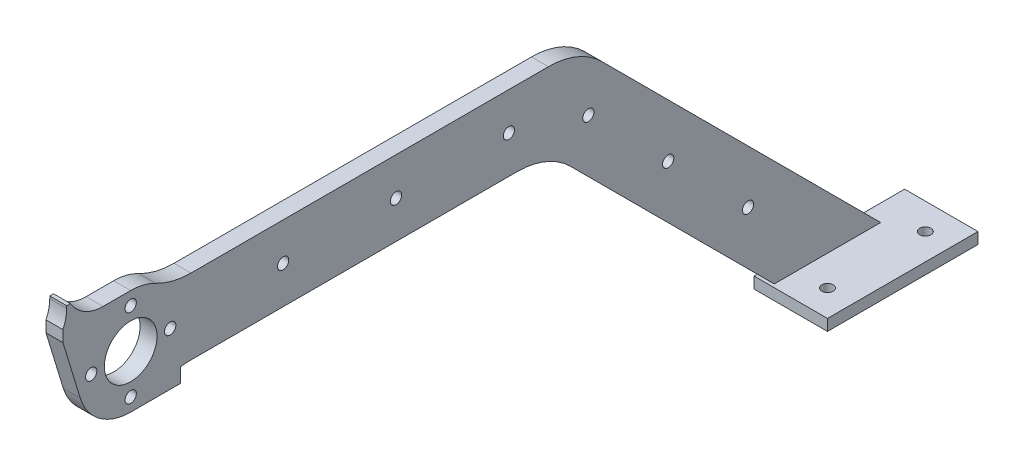
SolidWorks part; units mm, degrees
ref_plane "前视基准面" through (0, 0, 0) normal (0, 0, 1) x (1, 0, 0)
ref_plane "上视基准面" through (0, 0, 0) normal (0, 1, 0) x (1, 0, 0)
ref_plane "右视基准面" through (0, 0, 0) normal (1, 0, 0) x (0, 0, -1)
sketch "草图1" plane through (0, 0, 0) normal (1, 0, 0) x (0, 0, -1)
  line L2 (116.8579, -15.8579) -> (171, -70)
  line L3 (171, -70) -> (199.2843, -70)
  line L4 (199.2843, -70) -> (125.1421, 4.1421)
  line L5 (111, 10) -> (16, 10)
  line L7 (16, -10) -> (102.7369, -10)
  line L8 (186.193, -71.0509) -> (123.8062, -8.664) construction
  line L9 (0, 14) -> (-18, 14)
  line L10 (-18, 14) -> (-18, 11)
  line L11 (-18, 11) -> (-13.3889, -4.091)
  line L12 (13.2242, -14) -> (13.2242, -10)
  line L13 (0, -14) -> (13.2242, -14)
  arc A0 (6.5882, 12.3529) -> (6.5882, -12.3529) centre (0, 0) ccw
  circle A1 centre (0, 0) radius 10.5 construction
  circle A2 centre (0, 0) radius 7
  circle A3 centre (0, 10.5) radius 1.5
  circle A4 centre (10.5, 0) radius 1.5
  circle A5 centre (0, -10.5) radius 1.5
  circle A6 centre (-10.5, 0) radius 1.5
  arc A7 (125.1421, 4.1421) -> (111, 10) centre (111, -10) ccw
  arc A8 (102.7369, -10) -> (116.8579, -15.8579) centre (102.7157, -30) cw
  circle A9 centre (40.5, 0) radius 1.5
  circle A10 centre (70.5, 0) radius 1.5
  circle A11 centre (100.5, 0) radius 1.5
  circle A12 centre (121.61, -6.4679) radius 1.5
  circle A13 centre (142.8232, -27.6811) radius 1.5
  circle A14 centre (164.0364, -48.8943) radius 1.5
  arc A15 (16, 10) -> (6.5882, 12.3529) centre (16, 30) cw
  arc A16 (16, -10) -> (6.5882, -12.3529) centre (16, -30) ccw
  point P36 (185.1421, -70)
  point P43 (9.798, 7.7889)
  point P50 (9.798, -10)
  dimension "D1" = 28
  dimension "D2" = 21
  dimension "D3" = 14
  dimension "D4" = 3
  dimension "D9" = 20
  dimension "D13" = 3
  dimension "D16" = 30
  dimension "D17" = 3
  dimension "D19" = 30
  dimension "D24" = 20
  dimension "D25" = 20
  dimension "D6" = 135
  dimension "D7" = 20
  dimension "D8" = 171
  dimension "D10" = 70
  dimension "D11" = 20
  dimension "D14" = 40.5
  dimension "D18" = 21.11
  dimension "D20" = 30
  dimension "D21" = 18
  dimension "D22" = 3
  dimension "D26" = 13.2242
  dimension "D28" = 20
  dimension "D15" = 3
  dimension "D5" = 4
extrude "凸台-拉伸1" add sketch "草图1" along normal mid plane 4.5 contours A16 L7 A8 L2 L3 L4 A7 L5 A15 A0 A14 A13 A12 A11 A10 A9 A6 A5 A4 A3 A2 | A0 L9 L10 L11 | L12 A16 A0 region at (0, -9.4091, -111.2575) region at (0, -12.6228, -9.4909) region at (0, 9.7023, 13.097)
sketch "草图5" plane through (0, -70, 0) normal (0, -1, 0) x (1, 0, 0)
  line L0 (-2.25, -116.8579) -> (-2.25, -171) construction
  line L1 (-2.25, -170.1443) -> (17.25, -170.1443)
  line L2 (-2.25, -170.1443) -> (-2.25, -210.1443)
  line L3 (-2.25, -210.1443) -> (17.25, -210.1443)
  line L4 (17.25, -170.1443) -> (17.25, -210.1443)
  line L5 (2.25, -199.2843) -> (-2.25, -199.2843) construction
  dimension "D1" = 19.5
  dimension "D2" = 40
  dimension "D3" = 10.86
extrude "凸台-拉伸3" add sketch "草图5" along normal blind 3
sketch "草图6" plane through (0, -70, 0) normal (0, 1, 0) x (1, 0, 0)
  line L0 (17.25, 190.1443) -> (-2.25, 190.1443) construction
  line L1 (17.25, 210.1443) -> (17.25, 170.1443) construction
  line L2 (-2.25, 199.2843) -> (-2.25, 125.1421) construction
  line L3 (-2.25, 210.1443) -> (17.25, 210.1443) construction
  circle A0 centre (10.25, 203.1443) radius 1.5
  circle A1 centre (10.25, 177.1443) radius 1.5
  dimension "D3" = 3
  dimension "D1" = 7
  dimension "D2" = 7
extrude "切除-拉伸2" cut sketch "草图6" against normal through all
sketch "草图7" plane through (2.25, 0, 0) normal (1, 0, 0) x (0, 0, -1)
  line L1 (0, 14) -> (-18, 14) construction
  line L2 (-17.0011, 14) -> (-17.0011, 18.9987)
  line L3 (-17.0011, 18.9987) -> (-16.0023, 18.9987)
  line L4 (-16.0023, 18.9987) -> (-16.0023, 14)
  line L5 (-16.0023, 14) -> (-17.0011, 14)
extrude "凸台-拉伸4" add sketch "草图7" against normal up to vertex (4.5 mm away) up to point (-2.25, 14, 0)
fillet "圆角1" radius 10 2 edges at (0, 14, 16.0023) (0, 14, 17.0011)
